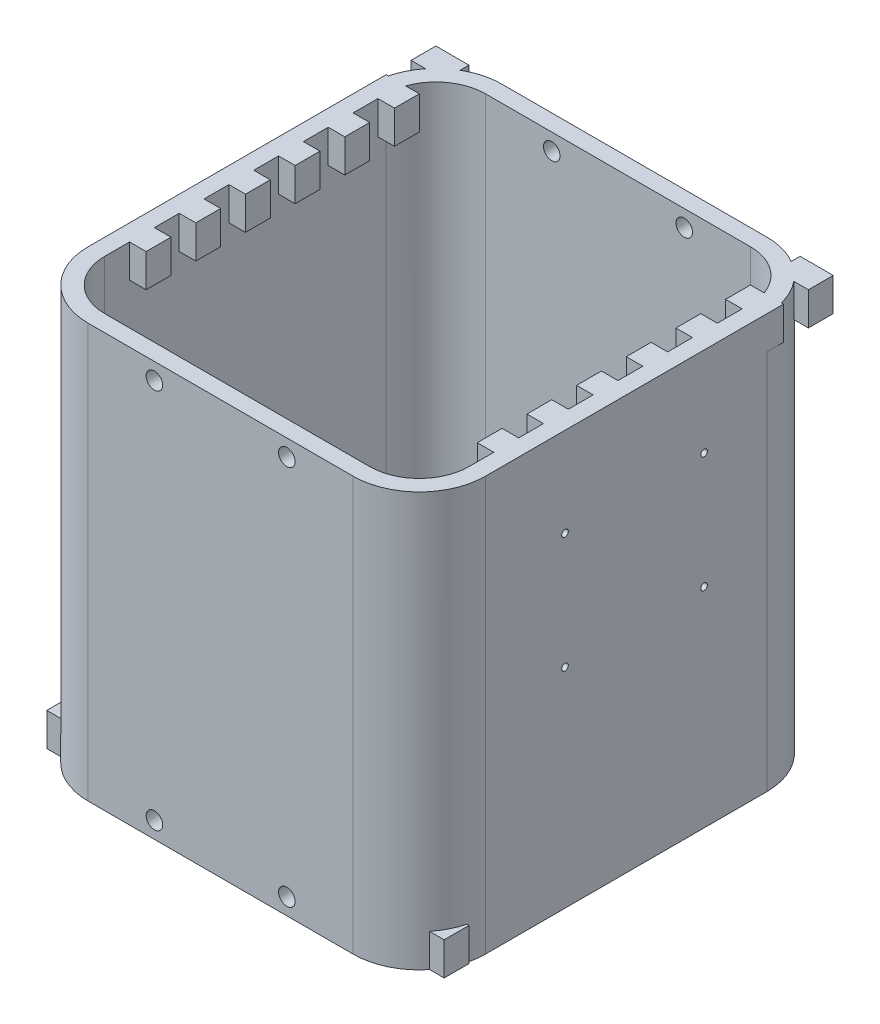
SolidWorks part; units mm, degrees
ref_plane "Front Plane" through (0, 0, 0) normal (0, 0, 1) x (1, 0, 0)
ref_plane "Top Plane" through (0, 0, 0) normal (0, 1, 0) x (1, 0, 0)
ref_plane "Right Plane" through (0, 0, 0) normal (1, 0, 0) x (0, 0, -1)
sketch "Sketch1" plane through (0, 0, 0) normal (0, 1, 0) x (1, 0, 0)
  line L0 (356.5379, 539.6819) -> (1600.9879, 539.6819) construction
  line L1 (-10, 30) -> (-10, 200)
  line L2 (30, 0) -> (190, 0)
  line L3 (0, 30) -> (0, 200)
  line L4 (30, 230) -> (190, 230)
  line L5 (220, 30) -> (220, 200)
  line L6 (30, 240) -> (190, 240)
  line L7 (230, 30) -> (230, 200)
  line L8 (30, -10) -> (190, -10)
  arc A0 (30, 230) -> (0, 200) centre (30, 200) ccw
  arc A1 (190, 230) -> (220, 200) centre (190, 200) cw
  arc A2 (220, 30) -> (190, 0) centre (190, 30) cw
  arc A3 (0, 30) -> (30, 0) centre (30, 30) ccw
  arc A4 (30, 240) -> (-10, 200) centre (30, 200) ccw
  arc A5 (190, 240) -> (230, 200) centre (190, 200) cw
  arc A6 (230, 30) -> (190, -10) centre (190, 30) cw
  arc A7 (-10, 30) -> (30, -10) centre (30, 30) ccw
  point P13 (220, 0)
  point P16 (0, 0)
  dimension "D3" = 30
  dimension "D1" = 230
  dimension "D2" = 220
  dimension "D4" = 10
extrude "Boss-Extrude1" add sketch "Sketch1" along normal blind 250
sketch "Sketch3" plane through (-10, 0, 0) normal (-1, 0, 0) x (0, 0, 1)
  line L1 (-200, 0) -> (-185, 0)
  line L2 (-200, 0) -> (-200, 20)
  line L3 (-200, 20) -> (-185, 20)
  line L4 (-185, 0) -> (-185, 20)
  line L5 (-185, 0) -> (-185, 20)
  line L6 (-185, 0) -> (-170, 0)
  line L7 (-170, 0) -> (-170, 20)
  line L8 (-185, 20) -> (-170, 20)
  line L9 (-170, 0) -> (-170, 20)
  line L10 (-170, 0) -> (-155, 0)
  line L11 (-155, 0) -> (-155, 20)
  line L12 (-170, 20) -> (-155, 20)
  line L13 (-155, 0) -> (-155, 20)
  line L14 (-155, 0) -> (-140, 0)
  line L15 (-140, 0) -> (-140, 20)
  line L16 (-155, 20) -> (-140, 20)
  line L17 (-140, 0) -> (-140, 20)
  line L18 (-140, 0) -> (-125, 0)
  line L19 (-125, 0) -> (-125, 20)
  line L20 (-140, 20) -> (-125, 20)
  line L21 (-125, 0) -> (-125, 20)
  line L22 (-125, 0) -> (-110, 0)
  line L23 (-110, 0) -> (-110, 20)
  line L24 (-125, 20) -> (-110, 20)
  line L25 (-110, 0) -> (-110, 20)
  line L26 (-110, 0) -> (-95, 0)
  line L27 (-95, 0) -> (-95, 20)
  line L28 (-110, 20) -> (-95, 20)
  line L29 (-95, 0) -> (-95, 20)
  line L30 (-95, 0) -> (-80, 0)
  line L31 (-80, 0) -> (-80, 20)
  line L32 (-95, 20) -> (-80, 20)
  line L33 (-80, 0) -> (-80, 20)
  line L34 (-80, 0) -> (-65, 0)
  line L35 (-65, 0) -> (-65, 20)
  line L36 (-80, 20) -> (-65, 20)
  line L37 (-65, 0) -> (-65, 20)
  line L38 (-65, 0) -> (-50, 0)
  line L39 (-50, 0) -> (-50, 20)
  line L40 (-65, 20) -> (-50, 20)
  line L41 (-50, 0) -> (-50, 20)
  line L42 (-50, 0) -> (-35, 0)
  line L43 (-35, 0) -> (-35, 20)
  line L44 (-50, 20) -> (-35, 20)
  line L45 (-35, 0) -> (-35, 20)
  line L46 (-35, 0) -> (-20, 0)
  line L47 (-20, 0) -> (-20, 20)
  line L48 (-35, 20) -> (-20, 20)
  line L49 (-20, 0) -> (-20, 20)
  line L50 (-20, 0) -> (-5, 0)
  line L51 (-5, 0) -> (-5, 20)
  line L52 (-20, 20) -> (-5, 20)
  line L53 (-5, 0) -> (-5, 20)
  line L54 (-5, 0) -> (10, 0)
  line L55 (10, 0) -> (10, 20)
  line L56 (-5, 20) -> (10, 20)
  line L57 (10, 0) -> (10, 20)
  line L58 (10, 0) -> (25, 0)
  line L59 (25, 0) -> (25, 20)
  line L60 (10, 20) -> (25, 20)
  line L61 (25, 0) -> (25, 20)
  line L62 (25, 0) -> (40, 0)
  line L63 (40, 0) -> (40, 20)
  line L64 (25, 20) -> (40, 20)
  line M3 (-200, 0) -> (-30, 0)
  line M5 (-30, 250) -> (-200, 250)
  line M6 (-200, 250) -> (-200, 0)
  dimension "D1" = 15
  dimension "D3" = 20
  dimension "D2" = 16
extrude "Boss-Extrude2" add sketch "Sketch3" against normal blind 20 contours L4 M3 M5 M6 | L11 L7 M3 M5 | L19 L15 M3 M5 | L35 L31 M3 M5 | L43 L39 M3 M5 | L51 L47 M3 M5 | L27 L28 L25 L26 region at (-10, 10, -192.5) region at (-10, 10, -162.5) region at (-10, 10, -132.5) region at (-10, 10, -72.5) region at (-10, 10, -42.5) region at (-10, 10, -12.5)
sketch "Sketch4" plane through (230, 0, 0) normal (1, 0, 0) x (0, 0, -1)
  line L1 (200, 0) -> (185, 0)
  line L2 (200, 0) -> (200, 20)
  line L3 (200, 20) -> (185, 20)
  line L4 (185, 0) -> (185, 20)
  line L5 (185, 0) -> (185, 20)
  line L6 (185, 0) -> (170, 0)
  line L7 (170, 0) -> (170, 20)
  line L8 (185, 20) -> (170, 20)
  line L9 (170, 0) -> (170, 20)
  line L10 (170, 0) -> (155, 0)
  line L11 (155, 0) -> (155, 20)
  line L12 (170, 20) -> (155, 20)
  line L13 (155, 0) -> (155, 20)
  line L14 (155, 0) -> (140, 0)
  line L15 (140, 0) -> (140, 20)
  line L16 (155, 20) -> (140, 20)
  line L17 (140, 0) -> (140, 20)
  line L18 (140, 0) -> (125, 0)
  line L19 (125, 0) -> (125, 20)
  line L20 (140, 20) -> (125, 20)
  line L21 (125, 0) -> (125, 20)
  line L22 (125, 0) -> (110, 0)
  line L23 (110, 0) -> (110, 20)
  line L24 (125, 20) -> (110, 20)
  line L25 (110, 0) -> (110, 20)
  line L26 (110, 0) -> (95, 0)
  line L27 (95, 0) -> (95, 20)
  line L28 (110, 20) -> (95, 20)
  line L29 (95, 0) -> (95, 20)
  line L30 (95, 0) -> (80, 0)
  line L31 (80, 0) -> (80, 20)
  line L32 (95, 20) -> (80, 20)
  line L33 (80, 0) -> (80, 20)
  line L34 (80, 0) -> (65, 0)
  line L35 (65, 0) -> (65, 20)
  line L36 (80, 20) -> (65, 20)
  line L37 (65, 0) -> (65, 20)
  line L38 (65, 0) -> (50, 0)
  line L39 (50, 0) -> (50, 20)
  line L40 (65, 20) -> (50, 20)
  line L41 (50, 0) -> (50, 20)
  line L42 (50, 0) -> (35, 0)
  line L43 (35, 0) -> (35, 20)
  line L44 (50, 20) -> (35, 20)
  line L45 (35, 0) -> (35, 20)
  line L46 (35, 0) -> (20, 0)
  line L47 (20, 0) -> (20, 20)
  line L48 (35, 20) -> (20, 20)
  line L49 (20, 0) -> (20, 20)
  line L50 (20, 0) -> (5, 0)
  line L51 (5, 0) -> (5, 20)
  line L52 (20, 20) -> (5, 20)
  line L53 (5, 0) -> (5, 20)
  line L54 (5, 0) -> (-10, 0)
  line L55 (-10, 0) -> (-10, 20)
  line L56 (5, 20) -> (-10, 20)
  line L57 (-10, 0) -> (-10, 20)
  line L58 (-10, 0) -> (-25, 0)
  line L59 (-25, 0) -> (-25, 20)
  line L60 (-10, 20) -> (-25, 20)
  line L61 (-25, 0) -> (-25, 20)
  line L62 (-25, 0) -> (-40, 0)
  line L63 (-40, 0) -> (-40, 20)
  line L64 (-25, 20) -> (-40, 20)
  line M5 (30, 0) -> (200, 0)
  line M6 (200, 0) -> (200, 250)
  line M7 (200, 250) -> (30, 250)
  dimension "D1" = 15
  dimension "D3" = 20
  dimension "D2" = 16
extrude "Boss-Extrude3" add sketch "Sketch4" against normal blind 20 contours L4 M5 M6 M7 | L11 L7 M5 M7 | L27 L23 M5 M7 | L35 L31 M5 M7 | L43 L39 M5 M7 | L51 L47 M5 M7 | L18 L19 L20 L17 region at (230, 10, -192.5) region at (230, 10, -162.5) region at (230, 10, -102.5) region at (230, 10, -72.5) region at (230, 10, -42.5) region at (230, 10, -12.5)
sketch "Sketch8" plane through (-10, 0, 0) normal (1, 0, 0) x (0, 0, -1)
  line L0 (45, 250) -> (45, 230)
  line L1 (30, 250) -> (45, 250)
  line L2 (30, 250) -> (30, 230)
  line L3 (30, 230) -> (45, 230)
  line L4 (45, 250) -> (45, 230)
  line L5 (45, 250) -> (60, 250)
  line L6 (60, 250) -> (60, 230)
  line L7 (45, 230) -> (60, 230)
  line L8 (60, 250) -> (60, 230)
  line L9 (60, 250) -> (75, 250)
  line L10 (75, 250) -> (75, 230)
  line L11 (60, 230) -> (75, 230)
  line L12 (75, 250) -> (75, 230)
  line L13 (75, 250) -> (90, 250)
  line L14 (90, 250) -> (90, 230)
  line L15 (75, 230) -> (90, 230)
  line L16 (90, 250) -> (90, 230)
  line L17 (90, 250) -> (105, 250)
  line L18 (105, 250) -> (105, 230)
  line L19 (90, 230) -> (105, 230)
  line L20 (105, 250) -> (105, 230)
  line L21 (105, 250) -> (120, 250)
  line L22 (120, 250) -> (120, 230)
  line L23 (105, 230) -> (120, 230)
  line L24 (120, 250) -> (120, 230)
  line L25 (120, 250) -> (135, 250)
  line L26 (135, 250) -> (135, 230)
  line L27 (120, 230) -> (135, 230)
  line L28 (135, 250) -> (135, 230)
  line L29 (135, 250) -> (150, 250)
  line L30 (150, 250) -> (150, 230)
  line L31 (135, 230) -> (150, 230)
  line L32 (150, 250) -> (150, 230)
  line L33 (150, 250) -> (165, 250)
  line L34 (165, 250) -> (165, 230)
  line L35 (150, 230) -> (165, 230)
  line L36 (165, 250) -> (165, 230)
  line L37 (165, 250) -> (180, 250)
  line L38 (180, 250) -> (180, 230)
  line L39 (165, 230) -> (180, 230)
  line L40 (180, 250) -> (180, 230)
  line L41 (180, 250) -> (195, 250)
  line L42 (195, 250) -> (195, 230)
  line L43 (180, 230) -> (195, 230)
  line L44 (195, 250) -> (195, 230)
  line L45 (195, 250) -> (210, 250)
  line L46 (210, 250) -> (210, 230)
  line L47 (195, 230) -> (210, 230)
  line L48 (210, 250) -> (210, 230)
  line L49 (210, 250) -> (225, 250)
  line L50 (225, 250) -> (225, 230)
  line L51 (210, 230) -> (225, 230)
  line L52 (225, 250) -> (225, 230)
  line L53 (225, 250) -> (240, 250)
  line L54 (240, 250) -> (240, 230)
  line L55 (225, 230) -> (240, 230)
  line L56 (240, 250) -> (240, 230)
  line L57 (240, 250) -> (255, 250)
  line L58 (255, 250) -> (255, 230)
  line L59 (240, 230) -> (255, 230)
  line L60 (255, 250) -> (255, 230)
  line L61 (255, 250) -> (270, 250)
  line L62 (270, 250) -> (270, 230)
  line L63 (255, 230) -> (270, 230)
  line L64 (30, 250) -> (45, 250) construction
  point P5 (37.5, 230)
  line M45 (30, 250) -> (200, 250)
  dimension "D1" = 15
  dimension "D2" = 20
  dimension "D4" = 15
  dimension "D3" = 16
extrude "Boss-Extrude5" add sketch "Sketch8" along normal blind 20 contours L39 L34 L38 M45 | L31 L26 L30 M45 | L23 L18 L22 M45 | L7 L0 L6 M45 | L54 L55 L52 L53 | L14 L15 L12 L13 | L44 L47 L46 L45 region at (-10, 240, -52.5) region at (-10, 240, -112.5) region at (-10, 240, -142.5) region at (-10, 240, -172.5)
sketch "Sketch9" plane through (230, 0, 0) normal (1, 0, 0) x (0, 0, -1)
  line L0 (45, 250) -> (45, 230)
  line L1 (30, 250) -> (45, 250)
  line L2 (30, 250) -> (30, 230)
  line L3 (30, 230) -> (45, 230)
  line L4 (45, 250) -> (45, 230)
  line L5 (45, 250) -> (60, 250)
  line L6 (60, 250) -> (60, 230)
  line L7 (45, 230) -> (60, 230)
  line L8 (60, 250) -> (60, 230)
  line L9 (60, 250) -> (75, 250)
  line L10 (75, 250) -> (75, 230)
  line L11 (60, 230) -> (75, 230)
  line L12 (75, 250) -> (75, 230)
  line L13 (75, 250) -> (90, 250)
  line L14 (90, 250) -> (90, 230)
  line L15 (75, 230) -> (90, 230)
  line L16 (90, 250) -> (90, 230)
  line L17 (90, 250) -> (105, 250)
  line L18 (105, 250) -> (105, 230)
  line L19 (90, 230) -> (105, 230)
  line L20 (105, 250) -> (105, 230)
  line L21 (105, 250) -> (120, 250)
  line L22 (120, 250) -> (120, 230)
  line L23 (105, 230) -> (120, 230)
  line L24 (120, 250) -> (120, 230)
  line L25 (120, 250) -> (135, 250)
  line L26 (135, 250) -> (135, 230)
  line L27 (120, 230) -> (135, 230)
  line L28 (135, 250) -> (135, 230)
  line L29 (135, 250) -> (150, 250)
  line L30 (150, 250) -> (150, 230)
  line L31 (135, 230) -> (150, 230)
  line L32 (150, 250) -> (150, 230)
  line L33 (150, 250) -> (165, 250)
  line L34 (165, 250) -> (165, 230)
  line L35 (150, 230) -> (165, 230)
  line L36 (165, 250) -> (165, 230)
  line L37 (165, 250) -> (180, 250)
  line L38 (180, 250) -> (180, 230)
  line L39 (165, 230) -> (180, 230)
  line L40 (180, 250) -> (180, 230)
  line L41 (180, 250) -> (195, 250)
  line L42 (195, 250) -> (195, 230)
  line L43 (180, 230) -> (195, 230)
  line L44 (195, 250) -> (195, 230)
  line L45 (195, 250) -> (210, 250)
  line L46 (210, 250) -> (210, 230)
  line L47 (195, 230) -> (210, 230)
  line L48 (210, 250) -> (210, 230)
  line L49 (210, 250) -> (225, 250)
  line L50 (225, 250) -> (225, 230)
  line L51 (210, 230) -> (225, 230)
  line L52 (225, 250) -> (225, 230)
  line L53 (225, 250) -> (240, 250)
  line L54 (240, 250) -> (240, 230)
  line L55 (225, 230) -> (240, 230)
  line L56 (240, 250) -> (240, 230)
  line L57 (240, 250) -> (255, 250)
  line L58 (255, 250) -> (255, 230)
  line L59 (240, 230) -> (255, 230)
  line L60 (255, 250) -> (255, 230)
  line L61 (255, 250) -> (270, 250)
  line L62 (270, 250) -> (270, 230)
  line L63 (255, 230) -> (270, 230)
  line L64 (30, 250) -> (45, 250) construction
  line M15 (200, 250) -> (30, 250)
  dimension "D1" = 20
  dimension "D2" = 15
  dimension "D4" = 15
  dimension "D3" = 16
extrude "Boss-Extrude6" add sketch "Sketch9" against normal blind 20 contours L10 L15 L14 M15 | L26 L31 L30 M15 | L34 L39 L38 M15 | L0 L7 L6 L5 | L23 L22 L21 L20 | L45 L46 L47 L44 | L52 L55 L54 L53 region at (230, 240, -82.5) region at (230, 240, -142.5) region at (230, 240, -172.5)
sketch "Sketch11" plane through (230, 0, 0) normal (1, 0, 0) x (0, 0, -1)
  line L0 (120, 250) -> (120, 0) construction
  line L1 (30, 250) -> (210, 250) construction
  line L2 (30, 0) -> (200, 0) construction
  line L3 (78, 250) -> (78, 0)
  line L4 (162, 250) -> (162, 0)
  line L5 (30, 125) -> (200, 125) construction
  line L6 (30, 250) -> (30, 0) construction
  line L7 (200, 230) -> (200, 0) construction
  line L8 (30, 125) -> (200, 125)
  line L9 (30, 195) -> (200, 195)
  line L10 (30, 197.2098) -> (30, 125)
  line L11 (200, 195) -> (200, 125) construction
  line L12 (30, 161.1049) -> (213.0514, 161.1049) construction
  circle A4 centre (78, 196.1049) radius 2
  circle A5 centre (78, 126.1049) radius 2
  circle A6 centre (162, 126.1049) radius 2
  circle A7 centre (162, 196.1049) radius 2
  dimension "D5" = 4
  dimension "D4" = 70
  dimension "D1" = 42
  dimension "D2" = 42
  dimension "D3" = 0
extrude "Cut-Extrude1" cut sketch "Sketch11" against normal blind 10 contours A4 | A7 | A6 | A5
sketch "Sketch12" plane through (0, 0, -240) normal (0, 0, -1) x (-1, 0, 0)
  line L0 (-110, 250) -> (-110, 0) construction
  line L1 (-190, 250) -> (-30, 250) construction
  line L2 (-190, 0) -> (-30, 0) construction
  line L3 (-190, 240) -> (-30, 240) construction
  line L6 (-190, 250) -> (-190, 0) construction
  line L7 (-30, 250) -> (-30, 0) construction
  line L8 (-190, 125) -> (-30, 125) construction
  circle A0 centre (-150, 240) radius 5
  circle A1 centre (-70, 240) radius 5
  circle A2 centre (-70, 10) radius 5
  circle A3 centre (-150, 10) radius 5
  dimension "D2" = 10
  dimension "D1" = 10
  dimension "D3" = 40
sketch "Sketch13" plane through (0, 0, 10) normal (0, 0, 1) x (1, 0, 0)
  line L0 (30, 125) -> (190, 125) construction
  line L1 (30, 250) -> (30, 0) construction
  line L2 (190, 250) -> (190, 0) construction
  circle A0 centre (70, 240) radius 5
  circle A1 centre (150, 240) radius 5
  circle A2 centre (150, 10) radius 5
  circle A3 centre (70, 10) radius 5
extrude "Cut-Extrude2" cut sketch "Sketch12" against normal blind 10
extrude "Cut-Extrude3" cut sketch "Sketch13" against normal blind 10
